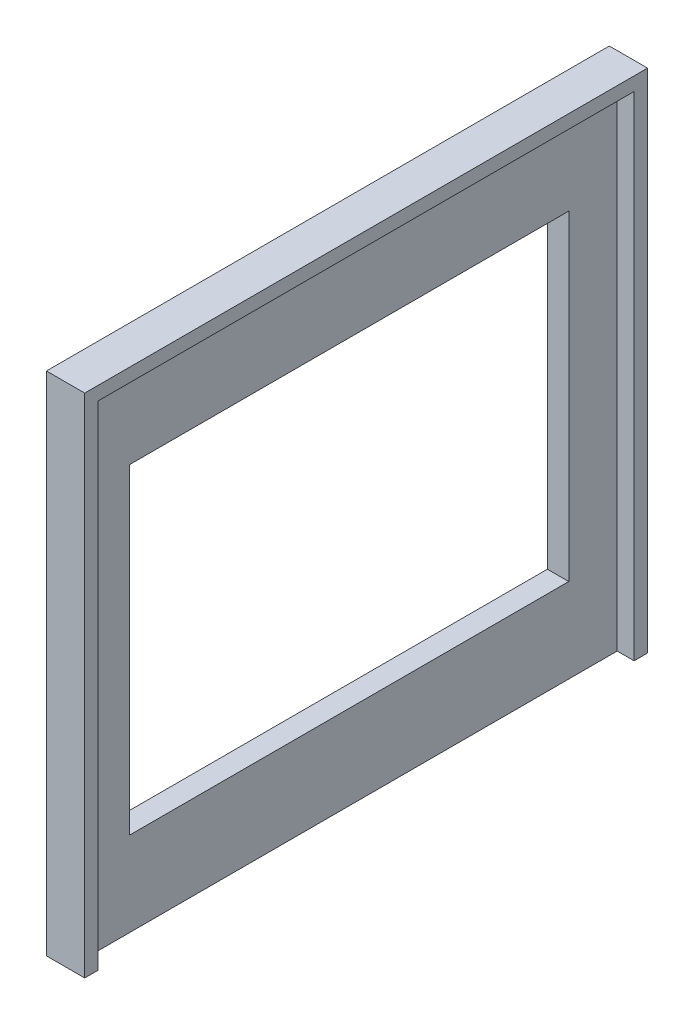
SolidWorks part; units mm, degrees
ref_plane "Front Plane" through (0, 0, 0) normal (0, 0, 1) x (1, 0, 0)
ref_plane "Top Plane" through (0, 0, 0) normal (0, 1, 0) x (1, 0, 0)
ref_plane "Right Plane" through (0, 0, 0) normal (1, 0, 0) x (0, 0, -1)
sketch "Sketch1" plane through (0, 0, 0) normal (1, 0, 0) x (0, 0, -1)
  line L1 (0, 0) -> (500, 0)
  line L2 (0, 0) -> (0, 450)
  line L3 (0, 450) -> (500, 450)
  line L4 (500, 0) -> (500, 450)
  line L5 (55, 360) -> (445, 360)
  line L6 (55, 360) -> (55, 75)
  line L7 (55, 75) -> (445, 75)
  line L8 (445, 360) -> (445, 75)
  dimension "D1" = 450
  dimension "D2" = 500
  dimension "D3" = 390
  dimension "D4" = 285
  dimension "D5" = 90
  dimension "D6" = 55
extrude "Boss-Extrude1" add sketch "Sketch1" along normal blind 19
sketch "Sketch2" plane through (19, 0, 0) normal (1, 0, 0) x (0, 0, -1)
  line L0 (500, 0) -> (500, 450) construction
  line L1 (0, 450) -> (500, 450)
  line L2 (0, 450) -> (0, 438)
  line L3 (0, 438) -> (500, 438)
  line L4 (500, 450) -> (500, 438)
  line L5 (0, 0) -> (500, 0) construction
  line L6 (0, 438) -> (12, 438)
  line L7 (0, 438) -> (0, 0)
  line L8 (0, 0) -> (12, 0)
  line L9 (12, 438) -> (12, 0)
  line L11 (500, 438) -> (488, 438)
  line L12 (500, 438) -> (500, 0)
  line L13 (500, 0) -> (488, 0)
  line L14 (488, 438) -> (488, 0)
  dimension "D1" = 12
extrude "Boss-Extrude4" add sketch "Sketch2" along normal blind 15 contours L7 L6 L9 L8
sketch "Sketch3" plane through (19, 0, 0) normal (1, 0, 0) x (0, 0, -1)
  line L0 (500, 0) -> (500, 450) construction
  line L1 (0, 450) -> (500, 450)
  line L2 (0, 450) -> (0, 438)
  line L3 (0, 438) -> (500, 438)
  line L4 (500, 450) -> (500, 438)
extrude "Boss-Extrude5" add sketch "Sketch3" along normal blind 15
sketch "Sketch4" plane through (19, 0, 0) normal (1, 0, 0) x (0, 0, -1)
  line L0 (500, 0) -> (500, 438) construction
  line L1 (500, 438) -> (488, 438)
  line L2 (500, 438) -> (500, 0)
  line L3 (500, 0) -> (488, 0)
  line L4 (488, 438) -> (488, 0)
  line L5 (12, 438) -> (500, 438) construction
  line L6 (12, 0) -> (500, 0) construction
extrude "Boss-Extrude6" add sketch "Sketch4" along normal blind 15
